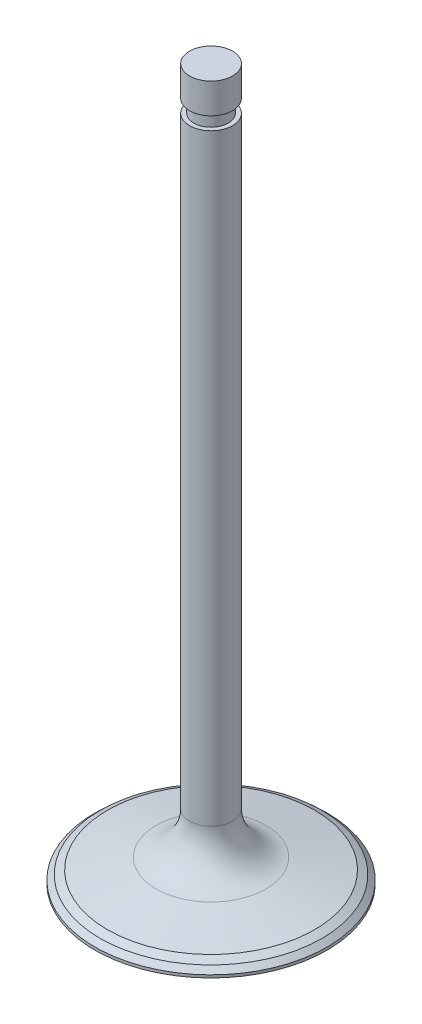
SolidWorks part; units mm, degrees
material "Vanadium"
ref_plane "Front Plane" through (0, 0, 0) normal (0, 0, 1) x (1, 0, 0)
ref_plane "Top Plane" through (0, 0, 0) normal (0, 1, 0) x (1, 0, 0)
ref_plane "Right Plane" through (0, 0, 0) normal (1, 0, 0) x (0, 0, -1)
sketch "Sketch1" plane through (0, 0, 0) normal (0, 0, 1) x (1, 0, 0)
  line L0 (0, 0) -> (0, 165)
  line L1 (0, 0) -> (-27, 0)
  line L2 (-27, 0) -> (-27, 2)
  line L3 (-27, 2) -> (-5, 7)
  line L4 (-5, 7) -> (-5, 155)
  line L5 (-5, 165) -> (0, 165)
  line L6 (-5, 158) -> (-4, 158)
  line L7 (-4, 158) -> (-4, 155)
  line L8 (-4, 155) -> (-5, 155)
  line L9 (-5, 158) -> (-5, 165)
  dimension "D1" = 165
  dimension "D2" = 5
  dimension "D3" = 27
  dimension "D4" = 2
  dimension "D5" = 7
  dimension "D6" = 3
  dimension "D7" = 1
  dimension "D8" = 7
revolve "Revolve1" add sketch "Sketch1" angle 360 about L0
fillet "Fillet1" radius 10 1 edges at (0, 7, -5)
chamfer "Chamfer1" distance 2 angle 30 1 edges at (0, 2, -27) first distance on face at (0, 5.231, -12.7838)
chamfer "Chamfer3" distance 1 angle 15 1 edges at (0, 2.4432, 25.0497) first distance on face at (0, 2.4432, 25.0497)
